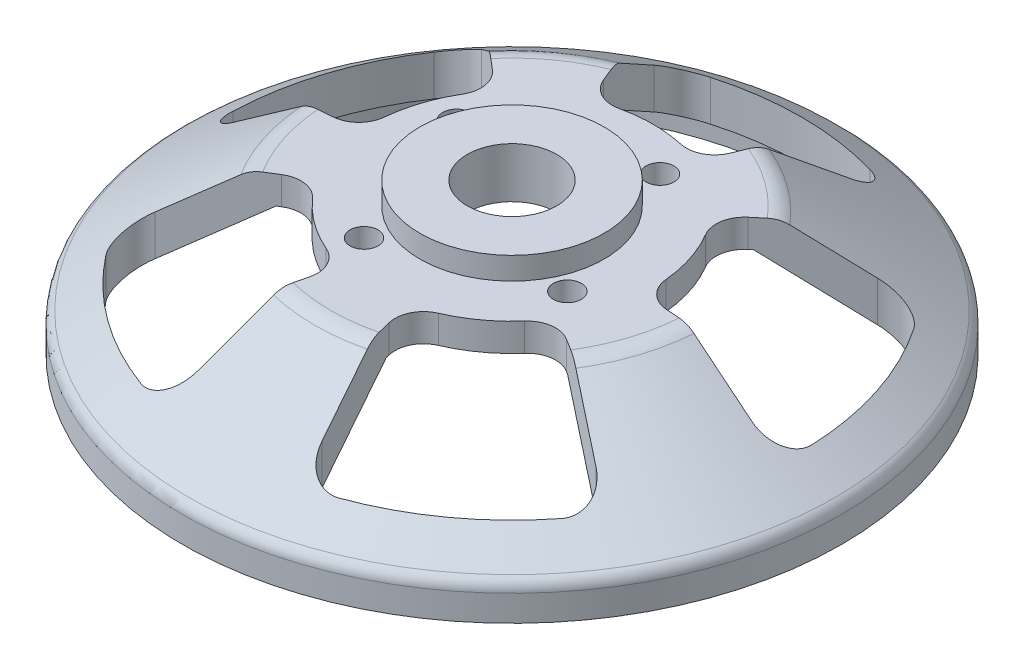
SolidWorks part; units mm, degrees
material "6061 Alloy"
ref_plane "Front Plane" through (0, 0, 0) normal (0, 0, 1) x (1, 0, 0)
ref_plane "Top Plane" through (0, 0, 0) normal (0, 1, 0) x (1, 0, 0)
ref_plane "Right Plane" through (0, 0, 0) normal (1, 0, 0) x (0, 0, -1)
sketch "Sketch1" plane through (0, 0, 0) normal (0, 0, 1) x (1, 0, 0)
  line L0 (0, 13.5) -> (0, 9)
  line L1 (29.5, 0) -> (29.5, 3)
  line L2 (29.5, 3) -> (17, 11.5)
  line L3 (17, 11.5) -> (8.25, 11.5)
  line L4 (8.25, 11.5) -> (8.25, 13.5)
  line L5 (8.25, 13.5) -> (0, 13.5)
  line L6 (26.5, 0) -> (29.5, 0)
  line L7 (0, 9) -> (15.3413, 9)
  line L8 (15.3413, 9) -> (26.5, 1.4121)
  line L9 (26.5, 1.4121) -> (26.5, 0)
  dimension "D1" = 13.5
  dimension "D2" = 3
  dimension "D3" = 8.25
  dimension "D4" = 2
  dimension "D5" = 29.5
  dimension "D7" = 2.5
  dimension "D8" = 3
  dimension "D9" = 3
revolve "Revolve2" add sketch "Sketch1" angle 360 about L0
sketch "Sketch2" plane through (0, 11.5, 0) normal (0, 1, 0) x (1, 0, 0)
  line L0 (0, 0) -> (0, 29.5) construction
  line L1 (-4.7963, 11.7055) -> (-9.7948, 23.9765)
  line L2 (4.7963, 11.7055) -> (9.7948, 23.9765)
  line L3 (9.6504, 8.1788) -> (19.7762, 16.7246)
  line L4 (12.6147, -0.9444) -> (25.8297, -1.9063)
  line L5 (10.7606, -6.6507) -> (22.0172, -13.6401)
  line L6 (3, -12.2891) -> (6.1688, -25.1546)
  line L7 (-3, -12.2891) -> (-6.1688, -25.1546)
  line L8 (-10.7606, -6.6507) -> (-22.0172, -13.6401)
  line L9 (-12.6147, -0.9444) -> (-25.8297, -1.9063)
  line L10 (-9.6504, 8.1788) -> (-19.7762, 16.7246)
  circle A0 centre (0, 0) radius 29.5 construction
  arc A1 (-4.7963, 11.7055) -> (4.7963, 11.7055) centre (0, 0) cw
  arc A2 (-9.7948, 23.9765) -> (9.7948, 23.9765) centre (0, 0) cw
  circle A3 centre (0, 0) radius 8.25 construction
  arc A4 (19.7762, 16.7246) -> (25.8297, -1.9063) centre (0, 0) cw
  arc A5 (9.6504, 8.1788) -> (12.6147, -0.9444) centre (0, 0) cw
  arc A6 (22.0172, -13.6401) -> (6.1688, -25.1546) centre (0, 0) cw
  arc A7 (10.7606, -6.6507) -> (3, -12.2891) centre (0, 0) cw
  arc A8 (-6.1688, -25.1546) -> (-22.0172, -13.6401) centre (0, 0) cw
  arc A9 (-3, -12.2891) -> (-10.7606, -6.6507) centre (0, 0) cw
  arc A10 (-25.8297, -1.9063) -> (-19.7762, 16.7246) centre (0, 0) cw
  arc A11 (-12.6147, -0.9444) -> (-9.6504, 8.1788) centre (0, 0) cw
  point P29 (0, 0)
  dimension "D1" = 3.6
  dimension "D2" = 4.4
  dimension "D4" = 6
  dimension "D3" = 5
extrude "Cut-Extrude1" cut sketch "Sketch2" against normal through all
fillet "Fillet1" radius 2.54 5 edges at (9.9923, 11.5, -13.7533) (16.168, 11.5, 5.2533) (0, 11.5, 17) (-16.168, 11.5, 5.2533) (-9.9923, 11.5, -13.7533)
fillet "Fillet2" radius 2.54 10 edges at (-12.6147, 10.25, 0.9444) (-9.6504, 10.25, -8.1788) (-4.7963, 10.25, -11.7055) (4.7963, 10.25, -11.7055) (9.6504, 10.25, -8.1788) (12.6147, 10.25, 0.9444) (10.7606, 10.25, 6.6507) (3, 10.25, 12.2891) (-3, 10.25, 12.2891) (-10.7606, 10.25, 6.6507)
fillet "Fillet3" radius 2.54 10 edges at (-25.8297, 3.6341, 1.9063) (-19.7762, 3.6341, -16.7246) (-9.7948, 3.6341, -23.9765) (9.7948, 3.6341, -23.9765) (19.7762, 3.6341, -16.7246) (25.8297, 3.6341, 1.9063) (22.0172, 3.6341, 13.6401) (6.1688, 3.6341, 25.1546) (-6.1688, 3.6341, 25.1546) (-22.0172, 3.6341, 13.6401)
fillet "Fillet4" radius 1.27 1 edges at (-29.5, 3, 0)
sketch "Sketch4" plane through (0, 11.5, 0) normal (0, 1, 0) x (1, 0, 0)
  line L0 (0, 0) -> (-11.5121, 5.2434) construction
  arc A0 (-10.8842, 6.4464) -> (-12.5946, 1.1823) centre (0, 0) ccw construction
  point P6 (-9.1005, 4.145)
  point P10 (4.145, 9.1005)
  point P11 (9.1005, -4.145)
  point P12 (-4.145, -9.1005)
  point P13 (0, 0)
  dimension "D1" = 10
  dimension "D2" = 4
hole_wizard "M3x0.5 Tapped Hole1" positions "Sketch6" profile "Sketch5" tap size "M3x0.5" standard "ANSI Metric" end condition through all
sketch "Sketch6" plane through (0, 11.5, 0) normal (0, 1, 0) x (1, 0, 0)
  point P0 (-9.1005, 4.145)
  point P3 (-4.145, -9.1005)
  point P6 (9.1005, -4.145)
  point P9 (4.145, 9.1005)
sketch "Sketch5" plane through (-9.1005, 11.5, -4.145) normal (1, 0, 0) x (0, 0, 1)
  line L0 (0, 0) -> (0, 11.5)
  line L1 (0, 11.5) -> (1.25, 11.5)
  line L2 (1.25, 11.5) -> (1.25, 0)
  line L5 (1.25, 0) -> (0, 0)
  line L11 (0, -6.35) -> (0, 107.95) construction
  dimension "Thru Tap Drill Dia." = 2.5
  dimension "Thru Tap Drill Depth" = 11.5
cosmetic thread "Hole Thread1" parameters "D2"=3
cosmetic thread "Hole Thread2" parameters "D2"=3
cosmetic thread "Hole Thread3" parameters "D2"=3
cosmetic thread "Hole Thread4" parameters "D2"=3
sketch "Sketch7" plane through (0, 13.5, 0) normal (0, 1, 0) x (1, 0, 0)
  circle A0 centre (0, 0) radius 4
  dimension "D1" = 8
extrude "Cut-Extrude2" cut sketch "Sketch7" against normal through all
